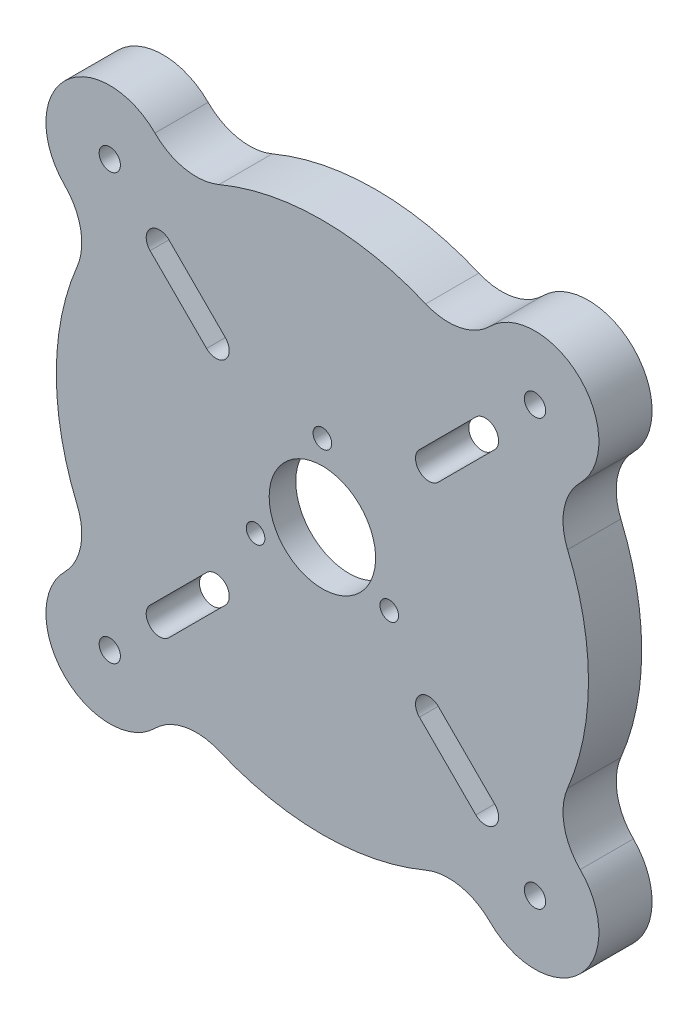
SolidWorks part; units mm, degrees
ref_plane "Front Plane" through (0, 0, 0) normal (0, 0, 1) x (1, 0, 0)
ref_plane "Top Plane" through (0, 0, 0) normal (0, 1, 0) x (1, 0, 0)
ref_plane "Right Plane" through (0, 0, 0) normal (1, 0, 0) x (0, 0, -1)
sketch "Sketch2" plane through (0, 0, 0) normal (0, 0, 1) x (1, 0, 0)
  line L0 (-39.9515, -39.9515) -> (39.9515, 39.9515) construction
  line L1 (-48.4368, -31.4663) -> (31.4663, 48.4368) construction
  line L2 (-31.4663, -48.4368) -> (48.4368, 31.4663) construction
  line L3 (0, 0) -> (0, 50) construction
  line L4 (39.9515, -39.9515) -> (-39.9515, 39.9515) construction
  line L5 (39.9515, -39.9515) -> (-39.9515, 39.9515) construction
  line L6 (31.4663, -48.4368) -> (-48.4368, 31.4663) construction
  line L7 (48.4368, -31.4663) -> (-31.4663, 48.4368) construction
  line L8 (20, 20) -> (30.6066, 30.6066) construction
  line L9 (18.2322, 21.7678) -> (28.8388, 32.3744)
  line L10 (21.7678, 18.2322) -> (32.3744, 28.8388)
  line L11 (20, -20) -> (30.6066, -30.6066) construction
  line L12 (21.7678, -18.2322) -> (32.3744, -28.8388)
  line L13 (18.2322, -21.7678) -> (28.8388, -32.3744)
  line L14 (-20, -20) -> (-30.6066, -30.6066) construction
  line L15 (-18.2322, -21.7678) -> (-28.8388, -32.3744)
  line L16 (-21.7678, -18.2322) -> (-32.3744, -28.8388)
  line L17 (-20, 20) -> (-30.6066, 30.6066) construction
  line L18 (-21.7678, 18.2322) -> (-32.3744, 28.8388)
  line L19 (-18.2322, 21.7678) -> (-28.8388, 32.3744)
  line L20 (0, 0) -> (50, 0) construction
  line L21 (0, 0) -> (0, -50) construction
  line L22 (0, 0) -> (-50, 0) construction
  circle A0 centre (0, 0) radius 50
  arc A1 (-48.4368, -31.4663) -> (-31.4663, -48.4368) centre (-39.9515, -39.9515) ccw construction
  arc A2 (48.4368, 31.4663) -> (31.4663, 48.4368) centre (39.9515, 39.9515) ccw construction
  arc A3 (31.4663, -48.4368) -> (48.4368, -31.4663) centre (39.9515, -39.9515) ccw construction
  arc A4 (-31.4663, 48.4368) -> (-48.4368, 31.4663) centre (-39.9515, 39.9515) ccw construction
  arc A5 (19.4135, 46.0773) -> (31.4663, 48.4368) centre (23.6858, 56.2173) ccw
  arc A6 (48.4368, 31.4663) -> (46.0773, 19.4135) centre (56.2173, 23.6858) ccw
  arc A7 (18.2322, 21.7678) -> (21.7678, 18.2322) centre (20, 20) ccw
  arc A8 (32.3744, 28.8388) -> (28.8388, 32.3744) centre (30.6066, 30.6066) ccw
  arc A9 (31.4663, 48.4368) -> (48.4368, 31.4663) centre (39.9515, 39.9515) cw
  arc A10 (48.4368, -31.4663) -> (31.4663, -48.4368) centre (39.9515, -39.9515) cw
  arc A11 (46.0773, -19.4135) -> (48.4368, -31.4663) centre (56.2173, -23.6858) ccw
  arc A12 (31.4663, -48.4368) -> (19.4135, -46.0773) centre (23.6858, -56.2173) ccw
  arc A13 (21.7678, -18.2322) -> (18.2322, -21.7678) centre (20, -20) ccw
  arc A14 (28.8388, -32.3744) -> (32.3744, -28.8388) centre (30.6066, -30.6066) ccw
  arc A15 (-31.4663, -48.4368) -> (-48.4368, -31.4663) centre (-39.9515, -39.9515) cw
  arc A16 (-19.4135, -46.0773) -> (-31.4663, -48.4368) centre (-23.6858, -56.2173) ccw
  arc A17 (-48.4368, -31.4663) -> (-46.0773, -19.4135) centre (-56.2173, -23.6858) ccw
  arc A18 (-18.2322, -21.7678) -> (-21.7678, -18.2322) centre (-20, -20) ccw
  arc A19 (-32.3744, -28.8388) -> (-28.8388, -32.3744) centre (-30.6066, -30.6066) ccw
  arc A20 (-48.4368, 31.4663) -> (-31.4663, 48.4368) centre (-39.9515, 39.9515) cw
  arc A21 (-46.0773, 19.4135) -> (-48.4368, 31.4663) centre (-56.2173, 23.6858) ccw
  arc A22 (-31.4663, 48.4368) -> (-19.4135, 46.0773) centre (-23.6858, 56.2173) ccw
  arc A23 (-21.7678, 18.2322) -> (-18.2322, 21.7678) centre (-20, 20) ccw
  arc A24 (-28.8388, 32.3744) -> (-32.3744, 28.8388) centre (-30.6066, 30.6066) ccw
  circle A25 centre (39.9515, 39.9515) radius 2
  circle A26 centre (39.9515, -39.9515) radius 2
  circle A27 centre (-39.9515, -39.9515) radius 2
  circle A28 centre (-39.9515, 39.9515) radius 2
  point P5 (0, 0)
  point P14 (0, 0)
  point P27 (25.3033, 25.3033)
  point P44 (25.3033, -25.3033)
  point P58 (-25.3033, -25.3033)
  point P72 (-25.3033, 25.3033)
  point P78 (0, 0)
  point P89 (0, 0)
  dimension "D1" = 100
  dimension "D2" = 12
  dimension "D5" = 2.5
  dimension "D10" = 4
  dimension "D3" = 113
  dimension "D4" = 45
  dimension "D6" = 15
  dimension "D7" = 20
  dimension "D8" = 4
  dimension "D9" = 4
extrude "Boss-Extrude2" add sketch "Sketch2" along normal blind 10 contours A9 A5 A0 A6 | A22 A20 A21 A0 | A17 A15 A16 A0 | A12 A10 A11 A0 | A0 A24 L19 A23 L18 A19 L16 A18 L15 A14 L13 A13 L12 A8 L10 A7 L9 region at (0, 0, 0) region at (35.6807, 35.6807, 0) region at (44.9674, -25.8881, 0) region at (-35.6807, 35.6807, 0) region at (-25.8881, -44.9674, 0)
sketch "Sketch3" plane through (0, 0, 0) normal (0, 0, -1) x (-1, 0, 0)
  line L0 (0, 14.5) -> (0, 0) construction
  circle A0 centre (0, 0) radius 21.25
  circle A1 centre (0, 14.5) radius 1.75
  circle A2 centre (12.5574, -7.25) radius 1.75
  circle A3 centre (-12.5574, -7.25) radius 1.75
  point P11 (0, 0)
  dimension "D1" = 42.5
  dimension "D2" = 3.5
  dimension "D3" = 14.5
  dimension "D4" = 3
extrude "Cut-Extrude2" cut sketch "Sketch3" against normal blind 5 contours A0 A3 A2 A1 | A1 | A2 | A3 region at (0, 0, 0) region at (0, 14.5, 0) region at (-12.5574, -7.25, 0) region at (12.5574, -7.25, 0)
extrude "Cut-Extrude3" cut sketch "Sketch3<3>" against normal through all contours A3 | A2 | A1 region at (0, 14.5, 0) region at (-12.5574, -7.25, 0) region at (12.5574, -7.25, 0)
sketch "Sketch3<3>" plane through (0, 0, 0) normal (0, 0, -1) x (-1, 0, 0) same geometry as "Sketch3"
sketch "Sketch4" plane through (0, 0, 5) normal (0, 0, -1) x (-1, 0, 0)
  circle A0 centre (0, 0) radius 10
  dimension "D1" = 20
extrude "Cut-Extrude4" cut sketch "Sketch4" against normal through all
